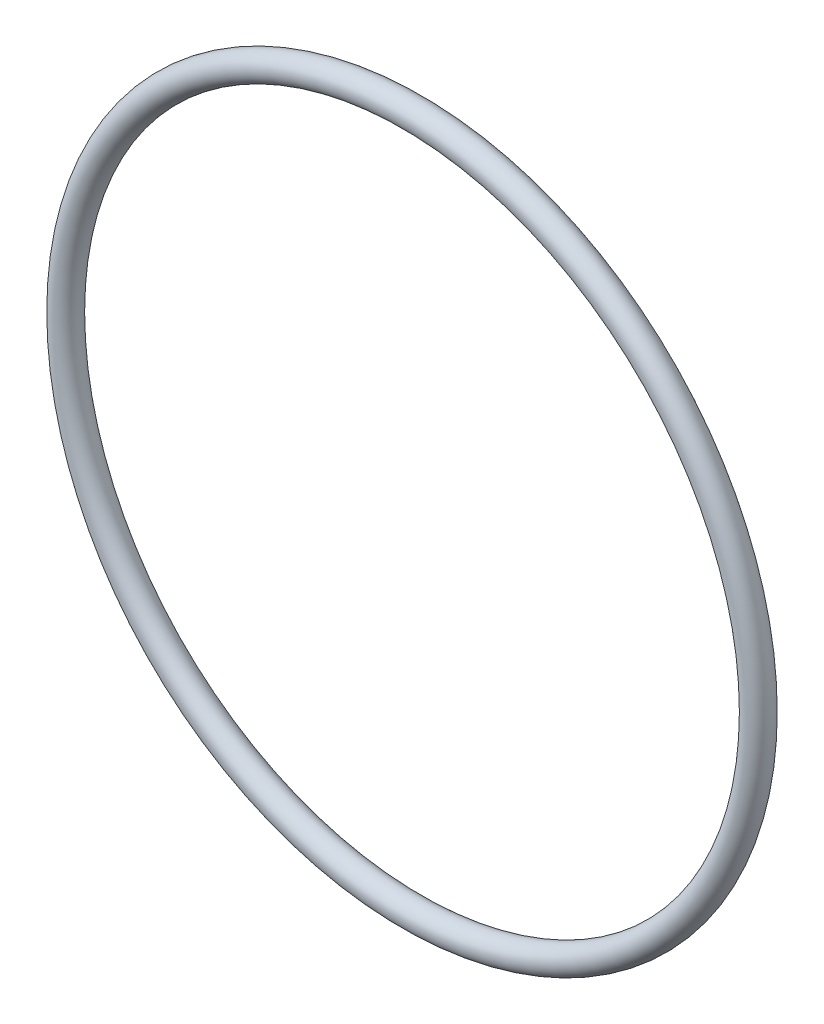
SolidWorks part; units mm, degrees
ref_plane "Front" through (0, 0, 0) normal (0, 0, 1) x (1, 0, 0)
ref_plane "Top" through (0, 0, 0) normal (0, 1, 0) x (1, 0, 0)
ref_plane "Right" through (0, 0, 0) normal (1, 0, 0) x (0, 0, -1)
sketch "Sketch1" plane through (0, 0, 0) normal (1, 0, 0) x (0, -1, 0)
  line L0 (0, -0.889) -> (0, 0.889) construction
  line L2 (-26.2496, 0) -> (26.2496, 0) construction
  line L3 (-22.0853, 0) -> (22.0853, 0) construction
  circle A0 centre (22.9743, 0) radius 0.889
  point P9 (22.0853, 0)
  point P10 (23.8633, 0)
  point P13 (22.9743, 0.889)
  point P14 (22.9743, -0.889)
  dimension "Width" = 1.778
  dimension "ID" = 44.1706
revolve "Revolve1" add sketch "Sketch1" angle 360 about L0
ref_plane "Plane1" through (0, 0, 0) normal (0, 0, 1) x (1, 0, 0)
ref_point "Point1"
ref_axis "Axis1" through (0, 0, 0) along (0, 0, 1)
